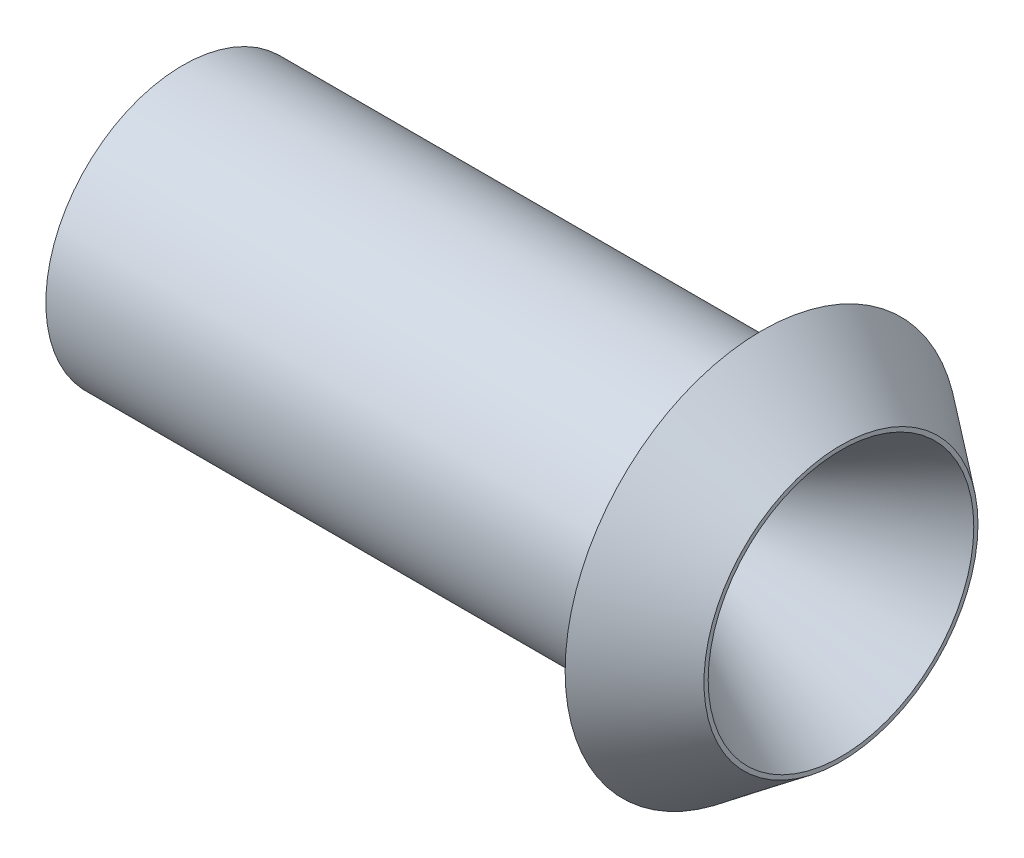
SolidWorks part; units mm, degrees
material "AISI 316 Annealed Stainless Steel Bar (SS)"
ref_plane "Front Plane" through (0, 0, 0) normal (0, 0, 1) x (1, 0, 0)
ref_plane "Top Plane" through (0, 0, 0) normal (0, 1, 0) x (1, 0, 0)
ref_plane "Right Plane" through (0, 0, 0) normal (1, 0, 0) x (0, 0, -1)
other "Configuration Table"
sketch "Sketch1" plane through (0, 0, 0) normal (0, 0, 1) x (1, 0, 0)
  line L0 (0, 0) -> (0, 8.255)
  line L1 (0, 8.255) -> (34.8804, 8.255)
  line L2 (34.8804, 8.255) -> (34.8804, 11.8491)
  line L3 (34.8804, 11.8491) -> (39.6499, 8.255)
  line L4 (39.6499, 8.255) -> (39.6499, 0)
  line L5 (39.6499, 0) -> (0, 0) construction
  line L7 (39.6499, 8.001) -> (30.6707, 2.8169)
  line L8 (30.6707, 2.8169) -> (29.4007, 2.8169)
  line L9 (29.4007, 2.8169) -> (0, 8.001)
  line L10 (0, 4.7625) -> (18.3664, 4.7625) construction
  line L11 (0, 3.175) -> (27.3696, 3.175) construction
  dimension "D1" = 16.51
  dimension "D2" = 34.8804
  dimension "D3" = 23.6982
  dimension "D4" = 37
  dimension "D5" = 0.254
  dimension "D6" = 0.254
  dimension "D7" = 30
  dimension "D8" = 29.4007
  dimension "ID" = 5.6337
  dimension "D9" = 1.27
  dimension "D10" = 10
  dimension "D11" = 3.175
  dimension "D12" = 4.7625
  dimension "D13" = 27.3696
  dimension "D14" = 18.3664
revolve "Revolve1" add sketch "Sketch1" angle 360 about L5 region at (23.9536, 6.5957, 0)
